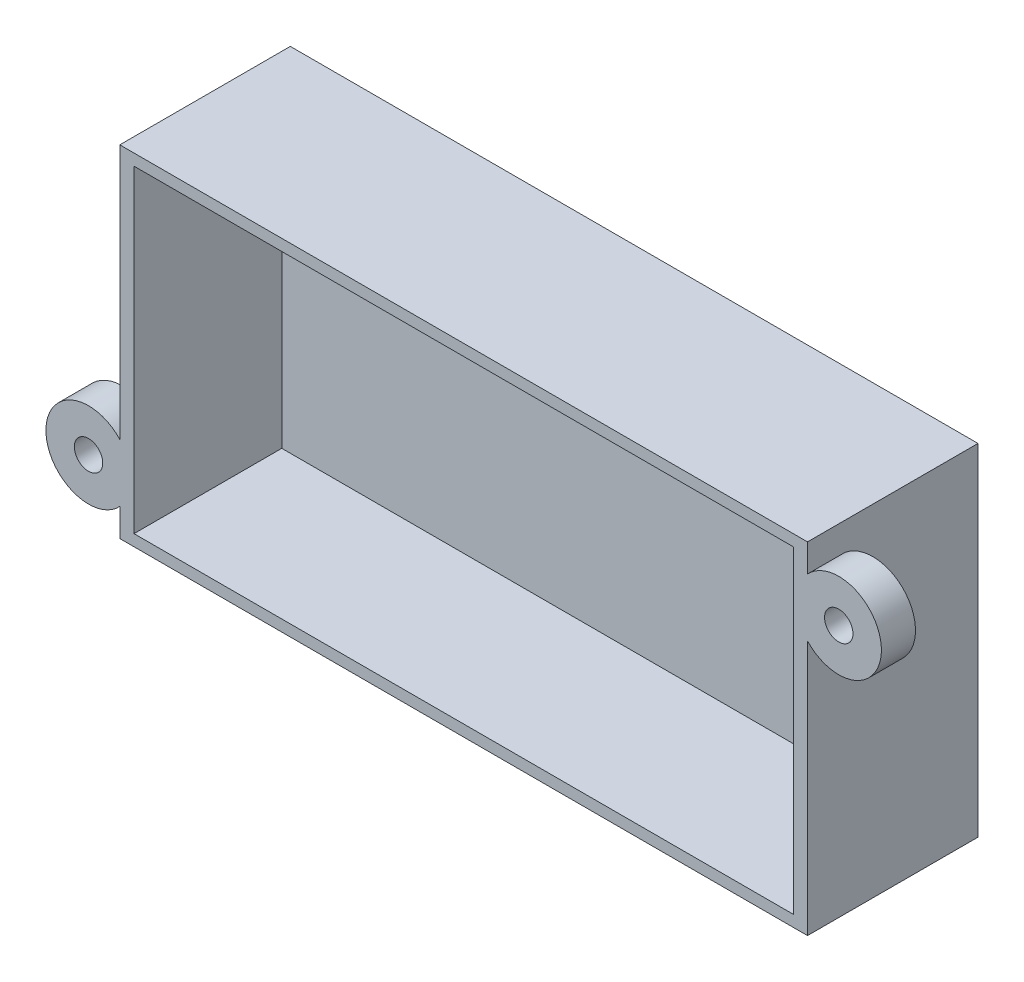
SolidWorks part; units mm, degrees
ref_plane "Ebene vorne" through (0, 0, 0) normal (0, 0, 1) x (1, 0, 0)
ref_plane "Ebene oben" through (0, 0, 0) normal (0, 1, 0) x (1, 0, 0)
ref_plane "Ebene rechts" through (0, 0, 0) normal (1, 0, 0) x (0, 0, -1)
sketch "Skizze1" plane through (0, 0, 0) normal (0, 0, 1) x (1, 0, 0)
  line L1 (-30.25, 15) -> (30.25, 15)
  line L2 (-30.25, 15) -> (-30.25, -15)
  line L3 (-30.25, -15) -> (30.25, -15)
  line L4 (30.25, 15) -> (30.25, -15)
  line L5 (-30.25, 15) -> (30.25, -15) construction
  line L6 (-30.25, -15) -> (30.25, 15) construction
  point P0 (0, 0)
  dimension "D1" = 60.5
  dimension "D2" = 30
extrude "Aufsatz-Linear austragen1" add sketch "Skizze1" along normal blind 15
sketch "Skizze2" plane through (0, 0, 15) normal (0, 0, 1) x (1, 0, 0)
  line L1 (-29, -14) -> (29, -14)
  line L2 (-29, -14) -> (-29, 14)
  line L3 (-29, 14) -> (29, 14)
  line L4 (29, -14) -> (29, 14)
  line L5 (-29, -14) -> (29, 14) construction
  line L6 (-29, 14) -> (29, -14) construction
  line L7 (-30.25, -7.4505) -> (-30.25, -12.5495)
  line L8 (-30.25, 15) -> (-30.25, -15) construction
  line L9 (-30.25, -15) -> (30.25, -15) construction
  line L10 (30.25, 12.5495) -> (30.25, 7.4505)
  line L11 (30.25, 15) -> (-30.25, 15) construction
  line L12 (30.25, -15) -> (30.25, 15) construction
  arc A1 (-30.25, -7.4505) -> (-30.25, -12.5495) centre (-33, -10) ccw
  circle A2 centre (-33, -10) radius 1.25
  circle A5 centre (33, 10) radius 1.25
  arc A6 (30.25, 12.5495) -> (30.25, 7.4505) centre (33, 10) cw
  point P0 (0, 0)
  line M5 (30.25, -15) -> (30.25, 15)
  line M7 (-30.25, 15) -> (-30.25, -15)
  dimension "D3" = 3.75
  dimension "D4" = 2.5
  dimension "D7" = 2.5
  dimension "D8" = 3.75
  dimension "D1" = 58
  dimension "D2" = 28
  dimension "D5" = 2.75
  dimension "D6" = 5
  dimension "D9" = 5
  dimension "D10" = 2.75
extrude "Schnitt-Linear austragen2" cut sketch "Skizze2" against normal blind 13
extrude "Aufsatz-Linear austragen2" add sketch "Skizze2<5>" against normal blind 3 contours A1 A2 M7 | A6 A5 M5 region at (-30.3492, -10, 15) region at (36.6508, 10, 15)
sketch "Skizze2<5>" plane through (0, 0, 15) normal (0, 0, 1) x (1, 0, 0) same geometry as "Skizze2"
